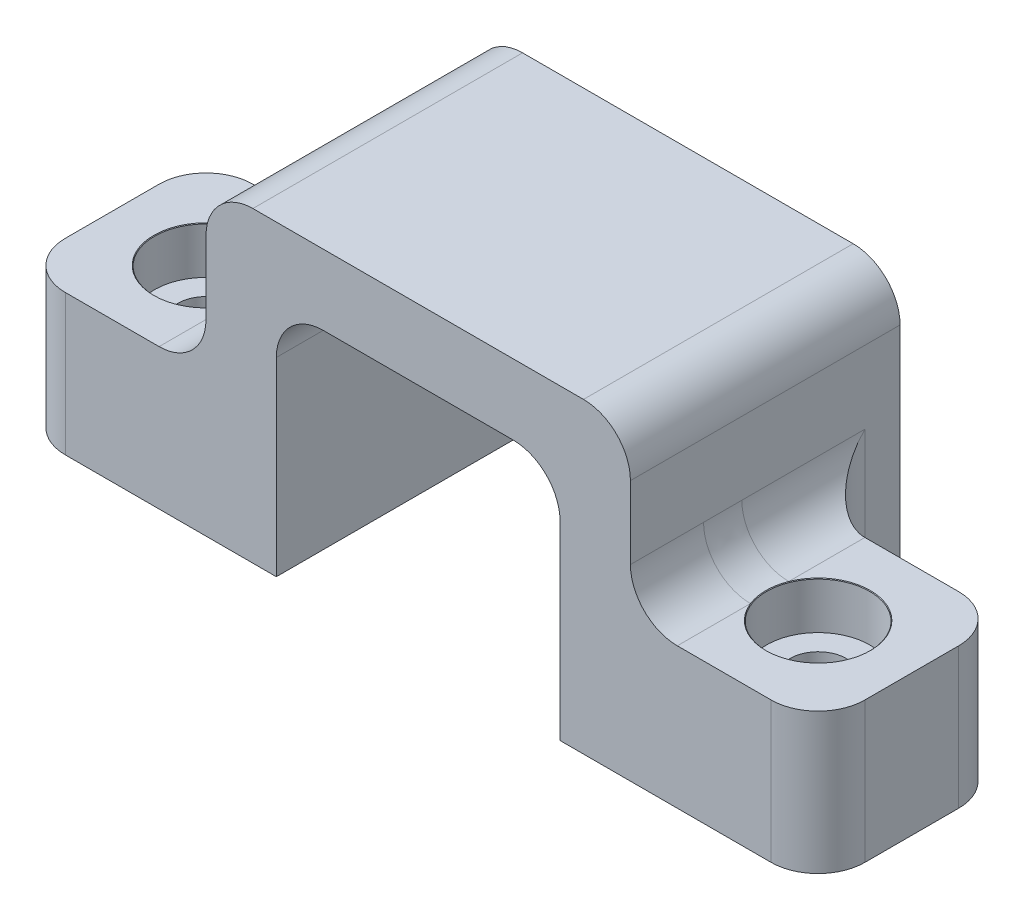
SolidWorks part; units mm, degrees
material "ABS"
ref_plane "Front Plane" through (0, 0, 0) normal (0, 0, 1) x (1, 0, 0)
ref_plane "Top Plane" through (0, 0, 0) normal (0, 1, 0) x (1, 0, 0)
ref_plane "Right Plane" through (0, 0, 0) normal (1, 0, 0) x (0, 0, -1)
sketch "Sketch1" plane through (0, 0, 0) normal (0, 0, 1) x (1, 0, 0)
  line L0 (-9.05, 0) -> (-6.05, 0)
  line L1 (-6.05, 0) -> (-6.05, 10.1)
  line L2 (-6.05, 10.1) -> (6.05, 10.1)
  line L3 (6.05, 10.1) -> (6.05, 0)
  line L4 (6.05, 0) -> (9.05, 0)
  line L5 (9.05, 0) -> (9.05, 13.1)
  line L6 (9.05, 13.1) -> (-9.05, 13.1)
  line L7 (-9.05, 13.1) -> (-9.05, 0)
  line L8 (0, 6.0974) -> (0, -4.8896) construction
  dimension "D1" = 3
  dimension "D2" = 3
  dimension "D3" = 10.1
  dimension "D4" = 12.1
extrude "Boss-Extrude1" add sketch "Sketch1" along normal blind 11.5
sketch "Sketch2" plane through (0, 0, 11.5) normal (0, 0, 1) x (1, 0, 0)
  line L0 (9.05, 0) -> (9.05, 13.1) construction
  line L1 (-9.05, 0) -> (-17.05, 0)
  line L2 (-9.05, 0) -> (-9.05, 6)
  line L3 (-9.05, 6) -> (-17.05, 6)
  line L4 (-17.05, 0) -> (-17.05, 6)
  line L5 (9.05, 0) -> (17.05, 0)
  line L6 (9.05, 0) -> (9.05, 6)
  line L7 (9.05, 6) -> (17.05, 6)
  line L8 (17.05, 0) -> (17.05, 6)
  line L9 (6.05, 0) -> (9.05, 0) construction
  dimension "D1" = 8
  dimension "D2" = 6
extrude "Boss-Extrude2" add sketch "Sketch2" against normal blind 8
hole_wizard "CBORE for M2 SHCS1" positions "Sketch3" profile "Sketch4" counterbore size "M2" standard "ANSI Metric" end condition through all
sketch "Sketch3" plane through (0, 6, 0) normal (0, 1, 0) x (1, 0, 0)
  line L0 (-13.05, -4.4865) -> (-13.05, -10.0625) construction
  line L2 (-16.4612, -7.5) -> (-10.1473, -7.5) construction
  line L4 (10.3318, -7.5642) -> (16.1332, -7.5642) construction
  line L5 (13.05, -4.3868) -> (13.05, -10.4342) construction
  line L6 (-9.05, -3.5) -> (-17.05, -3.5) construction
  line L7 (-9.05, -11.5) -> (-17.05, -11.5) construction
  line L8 (-17.05, -3.5) -> (-17.05, -11.5) construction
  line L9 (-9.05, -11.5) -> (-9.05, 0) construction
  line L10 (9.05, -11.5) -> (9.05, 0) construction
  line L11 (17.05, -3.5) -> (17.05, -11.5) construction
  point P0 (-13.05, -7.5)
  point P2 (13.1198, -7.5642)
sketch "Sketch4" plane through (-13.05, 6, 7.5) normal (1, 0, 0) x (0, 0, 1)
  line L0 (0, 0) -> (0, 6)
  line L1 (0, 6) -> (1.2, 6)
  line L3 (1.2, 6) -> (1.2, 2)
  line L4 (2.2, 2) -> (1.2, 2)
  line L5 (2.2, 2) -> (2.2, 0.025)
  line L6 (2.2, 0.025) -> (2.225, 0)
  line L7 (2.225, 0) -> (0, 0)
  line L8 (-2.2, 0.025) -> (-2.225, 0) construction
  line L11 (0, -6.35) -> (0, 107.95) construction
  dimension "Thru Hole Dia." = 2.4
  dimension "Thru Hole Depth" = 6
  dimension "C'Bore Dia." = 4.4
  dimension "C'Bore Depth" = 2
  dimension "Near C'Sink Dia." = 4.45
  dimension "Near C'Sink Angle" = 90
fillet "Fillet1" radius 2 12 edges at (-6.05, 10.1, 5.75) (6.05, 10.1, 5.75) (-9.05, 3, 3.5) (9.05, 3, 3.5) (17.05, 3, 3.5) (17.05, 3, 11.5) (9.05, 6, 7.5) (-17.05, 3, 3.5) (-17.05, 3, 11.5) (-9.05, 6, 7.5) (9.05, 13.1, 5.75) (-9.05, 13.1, 5.75)
